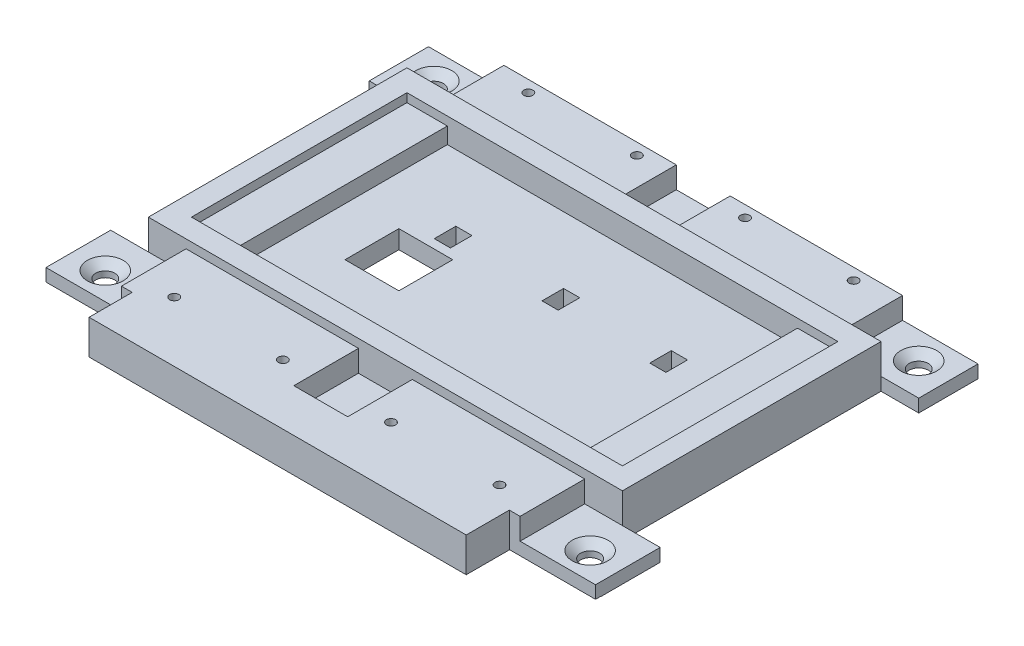
SolidWorks part; units mm, degrees
ref_plane "Front Plane" through (0, 0, 0) normal (0, 0, 1) x (1, 0, 0)
ref_plane "Top Plane" through (0, 0, 0) normal (0, 1, 0) x (1, 0, 0)
ref_plane "Right Plane" through (0, 0, 0) normal (1, 0, 0) x (0, 0, -1)
sketch "Sketch5" plane through (0, 5.08, 0) normal (0, 1, 0) x (1, 0, 0)
  line L0 (5.08, 5.08) -> (5.08, 248.92) construction
  line L1 (5.08, 105.41) -> (134.62, 105.41)
  line L2 (5.08, 105.41) -> (5.08, 16.51)
  line L3 (5.08, 16.51) -> (134.62, 16.51)
  line L4 (134.62, 105.41) -> (134.62, 16.51)
  line L6 (134.62, 248.92) -> (134.62, 5.08) construction
  point P8 (134.62, 60.96)
  dimension "D1" = 60.96
  dimension "D2" = 88.9
extrude "Button Support" add sketch "Sketch5" along normal blind 48.768
ref_plane "Plane1" through (0, 0, -60.96) normal (0, 0, 1) x (1, 0, 0)
sketch "Sketch6" plane through (0, 53.848, 0) normal (0, 1, 0) x (1, 0, 0)
  line L0 (0, 0) -> (139.7, 0) construction
  line L1 (19.05, 86.36) -> (120.65, 86.36)
  line L2 (19.05, 86.36) -> (19.05, 35.56)
  line L3 (19.05, 35.56) -> (120.65, 35.56)
  line L4 (120.65, 86.36) -> (120.65, 35.56)
  line L5 (125.73, 91.44) -> (13.97, 91.44)
  line L6 (125.73, 91.44) -> (125.73, 30.48)
  line L7 (125.73, 30.48) -> (13.97, 30.48)
  line L8 (13.97, 91.44) -> (13.97, 30.48)
  line L9 (134.62, 105.41) -> (5.08, 105.41) construction
  point P8 (69.85, 91.44)
  point P9 (69.85, 86.36)
  point P10 (120.65, 60.96)
  point P11 (125.73, 60.96)
  point P16 (69.85, 105.41)
  dimension "D1" = 50.8
  dimension "D2" = 60.96
  dimension "D3" = 101.6
  dimension "D4" = 5.08
  dimension "D5" = 5.08
extrude "Boss-Extrude4" add sketch "Sketch6" along normal blind 2.032
sketch "Sketch7" plane through (0, 53.848, 0) normal (0, 1, 0) x (1, 0, 0)
  line L0 (19.05, 35.56) -> (120.65, 35.56) construction
  line L1 (28.575, 35.56) -> (111.125, 35.56)
  line L2 (28.575, 35.56) -> (28.575, 86.36)
  line L3 (28.575, 86.36) -> (111.125, 86.36)
  line L4 (111.125, 35.56) -> (111.125, 86.36)
  line L5 (120.65, 86.36) -> (19.05, 86.36) construction
  point P8 (69.85, 86.36)
  point P9 (69.85, 35.56)
  dimension "D1" = 82.55
  dimension "D2" = 50.8
extrude "Force Sensor Cutout" cut sketch "Sketch7" against normal blind 3.81
sketch "Sketch4" plane through (0, 0, 0) normal (0, 0, 1) x (1, 0, 0)
  line L0 (0, 0) -> (139.7, 0) construction
  line L1 (5.08, 45.72) -> (134.62, 45.72)
  line L2 (5.08, 45.72) -> (5.08, 5.08)
  line L3 (5.08, 5.08) -> (134.62, 5.08)
  line L4 (134.62, 45.72) -> (134.62, 5.08)
  line L5 (0, 5.08) -> (0, 0) construction
  line L6 (139.7, 5.08) -> (139.7, 0) construction
  line L7 (0, 55.88) -> (139.7, 55.88) construction
  dimension "D1" = 5.08
  dimension "D2" = 5.08
  dimension "D3" = 5.08
  dimension "D4" = 10.16
extrude "Bottom Cut" cut sketch "Sketch4" against normal blind 139.7
sketch "Sketch8" plane through (0, 50.038, 0) normal (0, 1, 0) x (1, 0, 0)
  line L0 (120.65, 86.36) -> (19.05, 86.36) construction
  line L1 (71.628, 65.623) -> (75.438, 65.623)
  line L2 (71.628, 65.623) -> (71.628, 70.703)
  line L3 (71.628, 70.703) -> (75.438, 70.703)
  line L4 (75.438, 65.623) -> (75.438, 70.703)
  line L5 (120.65, 35.56) -> (120.65, 86.36) construction
  line L6 (97.028, 65.623) -> (97.028, 70.703)
  line L7 (97.028, 65.623) -> (100.838, 65.623)
  line L8 (100.838, 65.623) -> (100.838, 70.703)
  line L9 (97.028, 70.703) -> (100.838, 70.703)
  line L10 (46.228, 65.623) -> (46.228, 70.703)
  line L11 (46.228, 65.623) -> (50.038, 65.623)
  line L12 (50.038, 65.623) -> (50.038, 70.703)
  line L13 (46.228, 70.703) -> (50.038, 70.703)
  dimension "D1" = 15.657
  dimension "D2" = 45.212
  dimension "D3" = 3.81
  dimension "D4" = 5.08
  dimension "D5" = 2
  dimension "D6" = 2
extrude "Haptic Wire Holes" cut sketch "Sketch8" against normal up to surface (4.318 mm away) up to face at (69.85, 45.72, -60.96)
sketch "Sketch9" plane through (0, 50.038, 0) normal (0, 1, 0) x (1, 0, 0)
  line L0 (120.65, 86.36) -> (19.05, 86.36) construction
  line L1 (52.705, 63.5) -> (40.005, 63.5)
  line L2 (52.705, 63.5) -> (52.705, 50.8)
  line L3 (52.705, 50.8) -> (40.005, 50.8)
  line L4 (40.005, 63.5) -> (40.005, 50.8)
  line L5 (28.575, 86.36) -> (28.575, 35.56) construction
  dimension "D1" = 12.7
  dimension "D2" = 12.7
  dimension "D3" = 22.86
  dimension "D4" = 11.43
extrude "Force Sensor Hole" cut sketch "Sketch9" against normal up to surface (4.318 mm away) up to face at (48.133, 45.72, -68.163)
sketch "Sketch10" plane through (0, 53.848, 0) normal (0, 1, 0) x (1, 0, 0)
  line L0 (5.08, 16.51) -> (134.62, 16.51) construction
  line L1 (134.62, 105.41) -> (134.62, 16.51) construction
  line L2 (-26.8224, 60.96) -> (26.8224, 60.96) construction
  circle A0 centre (108.0186, 19.2295) radius 1.0795
  circle A4 centre (82.4261, 19.2295) radius 1.0795
  circle A5 centre (56.9186, 19.2295) radius 1.0795
  circle A6 centre (31.3261, 19.2295) radius 1.0795
  circle A7 centre (31.3261, 102.6905) radius 1.0795
  circle A8 centre (56.9186, 102.6905) radius 1.0795
  circle A9 centre (82.4261, 102.6905) radius 1.0795
  circle A10 centre (108.0186, 102.6905) radius 1.0795
  dimension "D1" = 2.159
  dimension "D2" = 2.7195
  dimension "D3" = 26.6014
  dimension "D5" = 25.5925
  dimension "D6" = 25.5075
  dimension "D4" = 25.5925
extrude "NeoPixel Holes" cut sketch "Sketch10" against normal up to surface (8.128 mm away) up to face at (46.355, 45.72, -57.15)
sketch "Sketch18" plane through (0, 53.848, 0) normal (0, 1, 0) x (1, 0, 0)
  line L0 (134.62, 248.92) -> (134.62, 5.08) construction
  line L1 (125.73, 91.44) -> (134.62, 91.44)
  line L2 (125.73, 91.44) -> (125.73, 30.48)
  line L3 (125.73, 30.48) -> (134.62, 30.48)
  line L4 (134.62, 91.44) -> (134.62, 30.48)
  line L5 (5.08, 105.41) -> (5.08, 16.51) construction
  line L6 (13.97, 91.44) -> (5.08, 91.44)
  line L7 (13.97, 91.44) -> (13.97, 30.48)
  line L8 (13.97, 30.48) -> (5.08, 30.48)
  line L9 (5.08, 91.44) -> (5.08, 30.48)
  line L10 (13.97, 30.48) -> (125.73, 30.48) construction
extrude "Neopixel Wire Side Holes" cut sketch "Sketch18" against normal up to next
sketch "Sketch19" plane through (0, 53.848, 0) normal (0, 1, 0) x (1, 0, 0)
  line L0 (25.4, 105.41) -> (5.08, 105.41) construction
  line L1 (76.2, 105.41) -> (63.5, 105.41)
  line L2 (76.2, 105.41) -> (76.2, 91.44)
  line L3 (76.2, 91.44) -> (63.5, 91.44)
  line L4 (63.5, 105.41) -> (63.5, 91.44)
  line L5 (22.86, 105.41) -> (5.08, 105.41)
  line L6 (22.86, 105.41) -> (22.86, 91.44)
  line L7 (22.86, 91.44) -> (5.08, 91.44)
  line L8 (5.08, 105.41) -> (5.08, 91.44)
  line L9 (5.08, 105.41) -> (5.08, 91.44) construction
  line L10 (134.62, 105.41) -> (5.08, 105.41) construction
  line L11 (134.62, 105.41) -> (116.84, 105.41)
  line L12 (134.62, 105.41) -> (134.62, 91.44)
  line L13 (134.62, 91.44) -> (116.84, 91.44)
  line L14 (116.84, 105.41) -> (116.84, 91.44)
  line L15 (125.73, 91.44) -> (13.97, 91.44) construction
  point P19 (69.85, 105.41)
  point P20 (69.85, 105.41)
  dimension "D1" = 12.7
  dimension "D2" = 17.78
extrude "NeoPixel solder gap" cut sketch "Sketch19" against normal blind 5.08
mirror "Mirror1" about plane through (0, 0, -60.96) normal (0, 0, 1) of "NeoPixel solder gap"
sketch "Sketch20" plane through (0, 0, -16.51) normal (0, 0, 1) x (1, 0, 0)
  line L0 (134.62, 48.768) -> (134.62, 45.72) construction
  line L1 (5.08, 48.768) -> (134.62, 48.768)
  line L2 (5.08, 48.768) -> (5.08, 45.7868)
  line L3 (5.08, 45.7868) -> (134.62, 45.7868)
  line L4 (134.62, 48.768) -> (134.62, 45.7868)
  line L6 (116.84, 53.848) -> (76.2, 53.848)
  line L7 (116.84, 53.848) -> (116.84, 48.768)
  line L8 (116.84, 48.768) -> (76.2, 48.768)
  line L9 (76.2, 53.848) -> (76.2, 48.768)
  line L10 (22.86, 53.848) -> (63.5, 53.848)
  line L11 (22.86, 53.848) -> (22.86, 48.768)
  line L12 (22.86, 48.768) -> (63.5, 48.768)
  line L13 (63.5, 53.848) -> (63.5, 48.768)
  line M5 (116.84, 48.768) -> (116.84, 53.848)
  line M6 (116.84, 53.848) -> (76.2, 53.848)
  line M7 (76.2, 53.848) -> (76.2, 48.768)
  line M8 (76.2, 48.768) -> (63.5, 48.768)
  line M9 (63.5, 48.768) -> (63.5, 53.848)
  line M10 (63.5, 53.848) -> (22.86, 53.848)
  line M11 (22.86, 53.848) -> (22.86, 48.768)
  line M12 (22.86, 48.768) -> (5.08, 48.768)
  line M13 (5.08, 48.768) -> (5.08, 45.72)
  line M15 (134.62, 45.72) -> (134.62, 48.768)
  line M16 (134.62, 48.768) -> (116.84, 48.768)
extrude "Boss-Extrude6" add sketch "Sketch20" along normal blind 1.27 contours L1 M7 M5 M6 | L3 L1 M13 M15 M16 M8 M12 | L1 M11 M9 M10 region at (69.85, 47.2774, -16.51) region at (43.18, 51.308, -16.51) region at (96.52, 51.308, -16.51)
sketch "Sketch11" plane through (0, 0, -15.24) normal (0, 0, 1) x (1, 0, 0)
  line L0 (5.08, 45.7868) -> (5.08, 45.72) construction
  line L1 (25.4, 53.848) -> (114.3, 53.848)
  line L2 (25.4, 53.848) -> (25.4, 45.72)
  line L3 (25.4, 45.72) -> (114.3, 45.72)
  line L4 (114.3, 53.848) -> (114.3, 45.72)
  line L5 (134.62, 45.7868) -> (134.62, 45.72) construction
  line L6 (5.08, 53.848) -> (134.62, 53.848) construction
  line L7 (5.08, 45.72) -> (134.62, 45.72) construction
  point P6 (0, 0)
  point P7 (0, 0)
  dimension "D1" = 20.32
  dimension "D2" = 20.32
extrude "Boss-Extrude5" add sketch "Sketch11" along normal blind 10.16
hole_wizard "CSK for #8 Flat Head Machine Screw (100)1" positions "Sketch21" profile "Sketch22" countersink size "#8" standard "ANSI Inch" end condition through all
sketch "Sketch21" plane through (0, 48.768, 0) normal (0, 1, 0) x (1, 0, 0)
  line L0 (134.62, 91.44) -> (134.62, 105.41) construction
  line L1 (134.62, 105.41) -> (116.84, 105.41) construction
  line L2 (22.86, 15.24) -> (5.08, 15.24) construction
  line L3 (5.08, 15.24) -> (5.08, 30.48) construction
  point P0 (12.7, 99.06)
  point P2 (127, 99.06)
  point P4 (127, 21.59)
  point P6 (12.7, 21.59)
  point P15 (127, 99.1921)
  point P18 (0, 0)
  point P19 (0, 0)
  point P20 (0, 0)
  point P21 (0, 0)
  point P28 (13.7101, 21.59)
  dimension "D1" = 7.62
  dimension "D2" = 6.35
  dimension "D3" = 6.35
  dimension "D4" = 7.62
sketch "Sketch22" plane through (12.7, 48.768, -99.06) normal (1, 0, 0) x (0, 0, 1)
  line L0 (0, 0) -> (0, 3.048)
  line L1 (0, 3.048) -> (2.2479, 3.048)
  line L2 (2.2479, 3.048) -> (2.2479, 1.6518)
  line L3 (2.2479, 1.6518) -> (4.2164, 0)
  line L5 (4.2164, 0) -> (0, 0)
  line L6 (-2.2479, 1.6518) -> (-4.2164, 0) construction
  line L11 (0, -6.35) -> (0, 107.95) construction
  dimension "Thru Hole Dia." = 4.4958
  dimension "Thru Hole Depth" = 3.048
  dimension "Near C'Sink Dia." = 8.4328
  dimension "Near C'Sink Angle" = 100
equation "\"Arrow Height\"= 1.5in"
equation "\"Button Height\"= 2in"
equation "\"Button Width\"= 4in"
equation "\"Haptic Diameter\"= 10mm"
equation "\"Haptic Thickness\"= 2.7mm"
equation "\"Arrow Spacing\"= 1in"
equation "\"Arrow Width\"= 1in"
equation "\"Haptic Wire Angle\"= 63.43"
equation "\"Haptic Wire Width\"= .1in"
equation "\"Haptic Wire Height\"= .15in"
equation "\"Mounting Bolt Hole Diameter\"= .14in"
